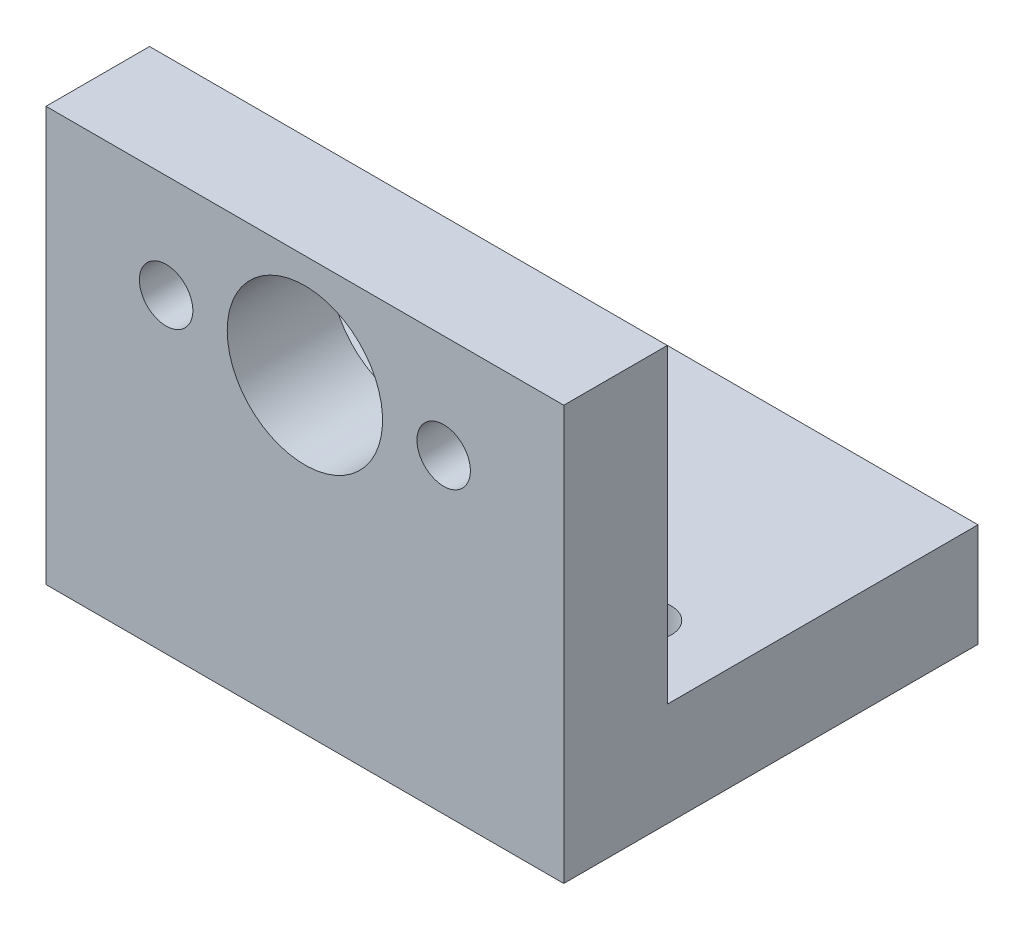
SolidWorks part; units mm, degrees
ref_plane "Front Plane" through (0, 0, 0) normal (0, 0, 1) x (1, 0, 0)
ref_plane "Top Plane" through (0, 0, 0) normal (0, 1, 0) x (1, 0, 0)
ref_plane "Right Plane" through (0, 0, 0) normal (1, 0, 0) x (0, 0, -1)
sketch "Sketch2" plane through (0, 0, 0) normal (1, 0, 0) x (0, 0, -1)
  line L0 (0, 0) -> (25.4, 0)
  line L1 (25.4, 0) -> (25.4, 6.35)
  line L2 (25.4, 6.35) -> (6.35, 6.35)
  line L3 (6.35, 6.35) -> (6.35, 25.4)
  line L4 (6.35, 25.4) -> (0, 25.4)
  line L5 (0, 25.4) -> (0, 0)
  dimension "D1" = 6.35
  dimension "D2" = 6.35
  dimension "D3" = 25.4
  dimension "D4" = 25.4
extrude "Boss-Extrude1" add sketch "Sketch2" along normal blind 31.75
sketch "Sketch3" plane through (0, 0, -6.35) normal (0, 0, -1) x (-1, 0, 0)
  line L1 (0, 6.35) -> (0, 25.4) construction
  line L2 (-31.75, 0) -> (0, 0) construction
  circle A0 centre (-15.875, 19.05) radius 4.7625
  circle A1 centre (-7.366, 19.05) radius 1.6383
  circle A2 centre (-24.384, 19.05) radius 1.6383
  dimension "D1" = 8.509
  dimension "D2" = 8.509
  dimension "D3" = 3.2766
  dimension "D4" = 3.2766
  dimension "D6" = 9.525
  dimension "D5" = 19.05
  dimension "D7" = 15.875
extrude "Cut-Extrude1" cut sketch "Sketch3" against normal through all
sketch "Sketch4" plane through (0, 6.35, 0) normal (0, 1, 0) x (1, 0, 0)
  line L0 (0, 25.4) -> (0, 6.35) construction
  line L1 (31.75, 25.4) -> (31.75, 6.35) construction
  line L2 (31.75, 25.4) -> (0, 25.4) construction
  circle A1 centre (5.08, 21.59) radius 1.524
  circle A2 centre (26.67, 10.16) radius 1.524
  dimension "D1" = 5.08
  dimension "D3" = 5.08
  dimension "D5" = 3.81
  dimension "D6" = 15.24
extrude "Cut-Extrude2" cut sketch "Sketch4" against normal through all
